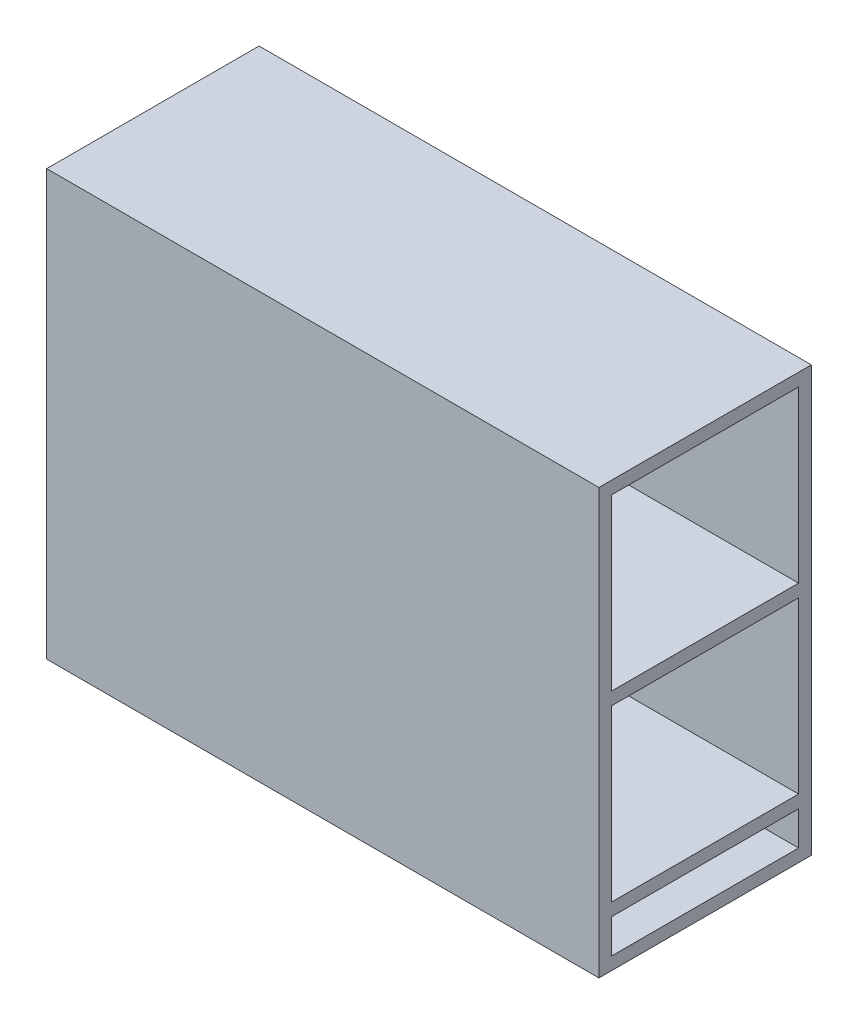
SolidWorks part; units mm, degrees
material "ABS"
ref_plane "Plan de face" through (0, 0, 0) normal (0, 0, 1) x (1, 0, 0)
ref_plane "Plan de dessus" through (0, 0, 0) normal (0, 1, 0) x (1, 0, 0)
ref_plane "Plan de droite" through (0, 0, 0) normal (1, 0, 0) x (0, 0, -1)
sketch "Esquisse1" plane through (0, 0, 0) normal (0, 1, 0) x (1, 0, 0)
  line L1 (0, 0) -> (130, 0)
  line L2 (0, 0) -> (0, 50)
  line L3 (0, 50) -> (130, 50)
  line L4 (130, 0) -> (130, 50)
extrude "Boss.-Extru.1" add sketch "Esquisse1" along normal blind 100
sketch "Esquisse2" plane through (130, 0, 0) normal (1, 0, 0) x (0, 0, -1)
  line L1 (0, 100) -> (50, 100) construction
  line L5 (3, 97) -> (3, 57)
  line L6 (3, 57) -> (47, 57)
  line L7 (47, 97) -> (47, 57)
  line L8 (3, 97) -> (47, 97)
  dimension "D1" = 40
  dimension "D2" = 3
extrude "Enlèv. mat.-Extru.1" cut sketch "Esquisse2" against normal offset from surface (127 mm away) 3 up to face at (0, 50, -25)
sketch "Esquisse3" plane through (130, 0, 0) normal (1, 0, 0) x (0, 0, -1)
  line L0 (47, 57) -> (47, 97) construction
  line L1 (3, 54) -> (47, 54)
  line L2 (3, 54) -> (3, 14)
  line L3 (3, 14) -> (47, 14)
  line L4 (47, 54) -> (47, 14)
  line L5 (3, 57) -> (47, 57) construction
  dimension "D1" = 40
  dimension "D2" = 3
extrude "Enlèv. mat.-Extru.2" cut sketch "Esquisse3" against normal offset from surface (127 mm away) 3 up to face at (0, 50, -25)
shell "Coque1" thickness 3 removed face at (130, 34, -25)
